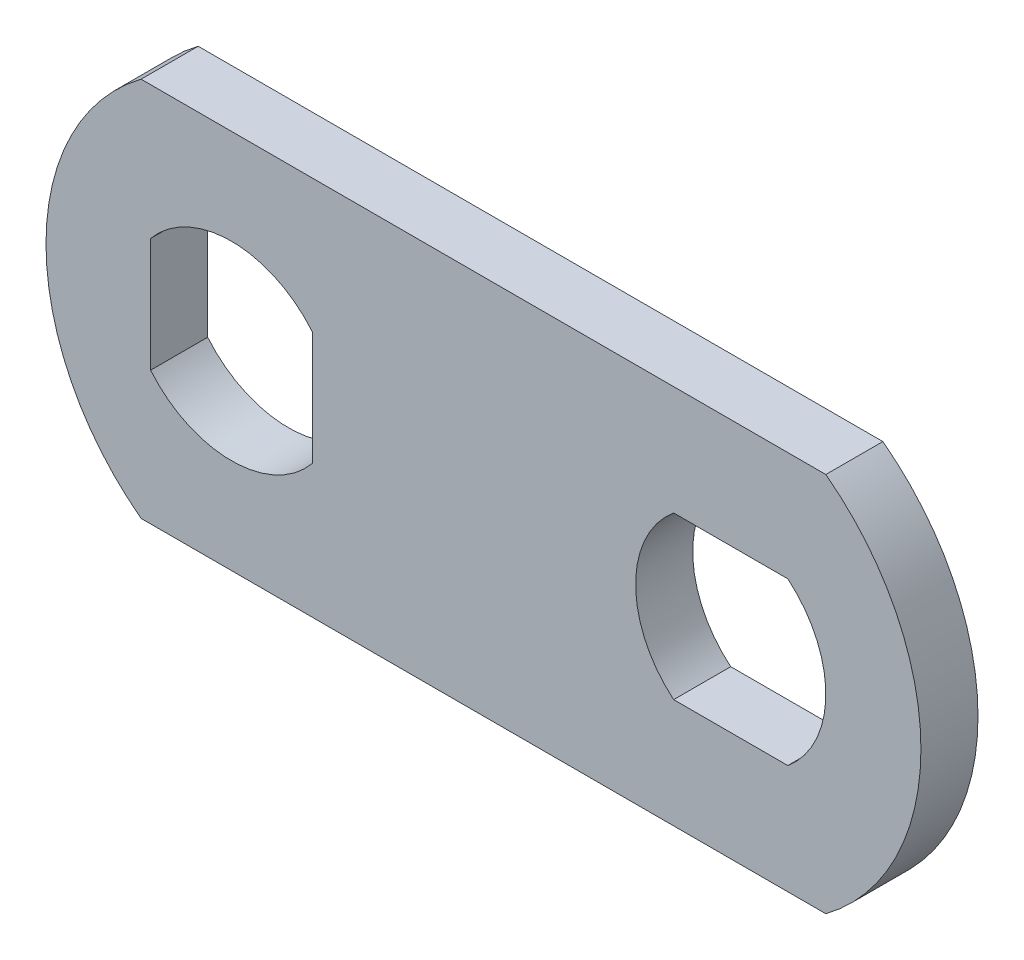
SolidWorks part; units mm, degrees
material "AISI 1020 Steel, Cold Rolled"
ref_plane "Front Plane" through (0, 0, 0) normal (0, 0, 1) x (1, 0, 0)
ref_plane "Top Plane" through (0, 0, 0) normal (0, 1, 0) x (1, 0, 0)
ref_plane "Right Plane" through (0, 0, 0) normal (1, 0, 0) x (0, 0, -1)
sketch "Sketch1" plane through (0, 0, 0) normal (0, 0, 1) x (1, 0, 0)
  line L0 (0, 0) -> (46, 0) construction
  line L1 (5, 10) -> (41, 10)
  line L2 (23, 0) -> (23, 10) construction
  line L3 (41, -10) -> (5, -10)
  arc A0 (41, 10) -> (41, -10) centre (33.5, 0) cw
  arc A1 (5, 10) -> (5, -10) centre (12.5, 0) ccw
  dimension "D3" = 12.5
  dimension "D4" = 21
  dimension "D1" = 20
  dimension "D2" = 46
sheet metal parameters "Sheet-Metal1" thickness 3 parameters "D1"=1
base flange "Base-Flange1" sketch "Sketch1" thickness 3 reverse thickness direction no parameters "D1"=1
sketch "Sketch4" plane through (0, 0, 0) normal (0, 0, 1) x (1, 0, 0)
  line L0 (0, 0) -> (46, 0) construction
  line L1 (5.5, 3) -> (5.5, -3)
  line L2 (14, 3) -> (14, -3)
  line L3 (5.5, 3) -> (14, 3) construction
  line L4 (39, 4.25) -> (39, -4.25) construction
  line L5 (5.5, 5) -> (14, 5) construction
  line L6 (39, 4.25) -> (33, 4.25)
  line L7 (31, 0) -> (41, 0) construction
  line L8 (39, -4.25) -> (33, -4.25)
  arc A0 (41, -10) -> (41, 10) centre (33.5, 0) ccw construction
  arc A1 (5.5, 3) -> (14, 3) centre (9.75, -0.5156) cw
  arc A2 (5.5, -3) -> (14, -3) centre (9.75, 0.5156) ccw
  arc A3 (39, 4.25) -> (39, -4.25) centre (35.4844, 0) cw
  arc A4 (33, 4.25) -> (33, -4.25) centre (36.5156, 0) ccw
  point P22 (9.75, -5)
  dimension "D1" = 5.5
  dimension "D3" = 8.5
  dimension "D4" = 2
  dimension "D5" = 1.0312
  dimension "D6" = 5.5156
  dimension "D7" = 5.5156
  dimension "D2" = 8.5
  dimension "D8" = 5
extrude "Cut-Extrude1" cut sketch "Sketch4" against normal blind 10 normal cut yes
flat pattern "Flat-Pattern1" [suppressed]
sketch "Bend-Lines1" plane through (0, 0, 0) normal (0, 1, 0) x (-1, 0, 0)
sketch3d "Bounding-Box1" [suppressed]
  line L0 (33.5, -10, 0) -> (-12.5, -10, 0) construction
  line L1 (33.5, 10, 0) -> (-12.5, 10, 0) construction
  line L2 (33.5, -10, 0) -> (33.5, 10, 0) construction
  line L3 (-12.5, -10, 0) -> (-12.5, 10, 0) construction
